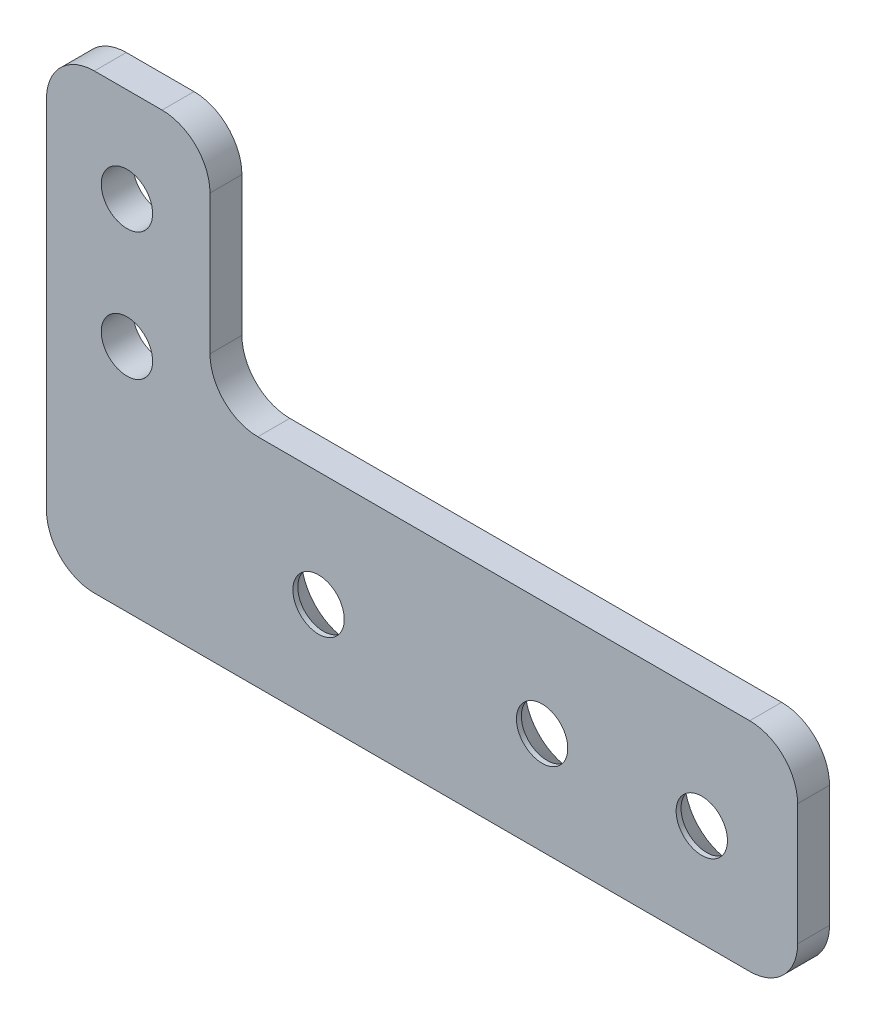
SolidWorks part; units mm, degrees
material "6061-T6 (SS)"
ref_plane "Front Plane" through (0, 0, 0) normal (0, 0, 1) x (1, 0, 0)
ref_plane "Top Plane" through (0, 0, 0) normal (0, 1, 0) x (1, 0, 0)
ref_plane "Right Plane" through (0, 0, 0) normal (1, 0, 0) x (0, 0, -1)
sketch "Sketch1" plane through (0, 0, 0) normal (0, 0, 1) x (1, 0, 0)
  line L0 (41.275, -11.049) -> (-33.401, -11.049) construction
  line L1 (-41.275, -23.749) -> (41.275, -23.749)
  line L2 (-41.275, -23.749) -> (-41.275, 23.749)
  line L3 (-41.275, 23.749) -> (41.275, 23.749)
  line L4 (41.275, -23.749) -> (41.275, 23.749)
  line L5 (-41.275, -23.749) -> (41.275, 23.749) construction
  line L6 (-41.275, 23.749) -> (41.275, -23.749) construction
  line L7 (41.275, 23.749) -> (-17.145, 23.749)
  line L8 (41.275, 23.749) -> (41.275, 0.381)
  line L9 (41.275, 0.381) -> (-17.145, 0.381)
  line L10 (-17.145, 23.749) -> (-17.145, 0.381)
  line L11 (-41.275, -23.749) -> (-33.401, -23.749)
  line L12 (-41.275, -23.749) -> (-41.275, 23.749)
  line L13 (-41.275, 23.749) -> (-33.401, 23.749)
  line L14 (-33.401, -23.749) -> (-33.401, 23.749)
  line L15 (-33.401, -23.749) -> (41.275, -23.749)
  line L16 (-33.401, -23.749) -> (-33.401, -21.209)
  line L17 (-33.401, -21.209) -> (41.275, -21.209)
  line L18 (41.275, -23.749) -> (41.275, -21.209)
  line L19 (-33.401, 23.876) -> (-17.145, 23.876) construction
  circle A0 centre (-25.4, -11.049) radius 2.5527
  circle A1 centre (-25.4, 1.651) radius 2.5527
  circle A2 centre (-25.4, 14.351) radius 2.5527
  point P0 (0, 0)
  point P22 (31.75, -11.049)
  point P23 (-6.35, -11.049)
  point P24 (15.875, -11.049)
  dimension "D7" = 5.1054
  dimension "D1" = 82.55
  dimension "D2" = 47.498
  dimension "D3" = 24.13
  dimension "D4" = 24.13
  dimension "D5" = 7.874
  dimension "D6" = 47.498
  dimension "D8" = 19.05
  dimension "D9" = 12.7
  dimension "D10" = 12.7
  dimension "D11" = 12.7
  dimension "D12" = 9.525
  dimension "D13" = 38.1
  dimension "D14" = 22.225
  dimension "D15" = 8.001
  dimension "D16" = 2.54
extrude "Boss-Extrude1" add sketch "Sketch1" along normal blind 3.175 contours L14 L17 L4 L9 L10 L3 A2 A1 A0 | A0 region at (-0.8769, -6.375, 0) region at (-25.4, -11.049, 0)
fillet "Fillet1" radius 4.7625 6 edges at (-33.401, 23.749, 1.5875) (-17.145, 23.749, 1.5875) (-17.145, 0.381, 1.5875) (41.275, 0.381, 1.5875) (41.275, -21.209, 1.5875) (-33.401, -21.209, 1.5875)
hole_wizard "CSK for #10 Flat Head Machine Screw3" positions "Sketch6" profile "Sketch7" countersink size "#10" standard "ANSI Inch" end condition through all
sketch "Sketch6" plane through (0, 0, 0) normal (0, 0, -1) x (-1, 0, 0)
  point P0 (-31.75, -11.049)
  point P3 (-15.875, -11.049)
  point P6 (6.35, -11.049)
sketch "Sketch7" plane through (31.75, -11.049, 0) normal (1, 0, 0) x (0, 1, 0)
  line L0 (0, 0) -> (0, 3.175)
  line L1 (0, 3.175) -> (2.5527, 3.175)
  line L2 (2.5527, 3.175) -> (2.5527, 2.6882)
  line L3 (2.5527, 2.6882) -> (4.8895, 0)
  line L5 (4.8895, 0) -> (0, 0)
  line L6 (-2.5527, 2.6882) -> (-4.8895, 0) construction
  line L11 (0, -6.35) -> (0, 107.95) construction
  dimension "Thru Hole Dia." = 5.1054
  dimension "Thru Hole Depth" = 3.175
  dimension "Near C'Sink Dia." = 9.779
  dimension "Near C'Sink Angle" = 82
